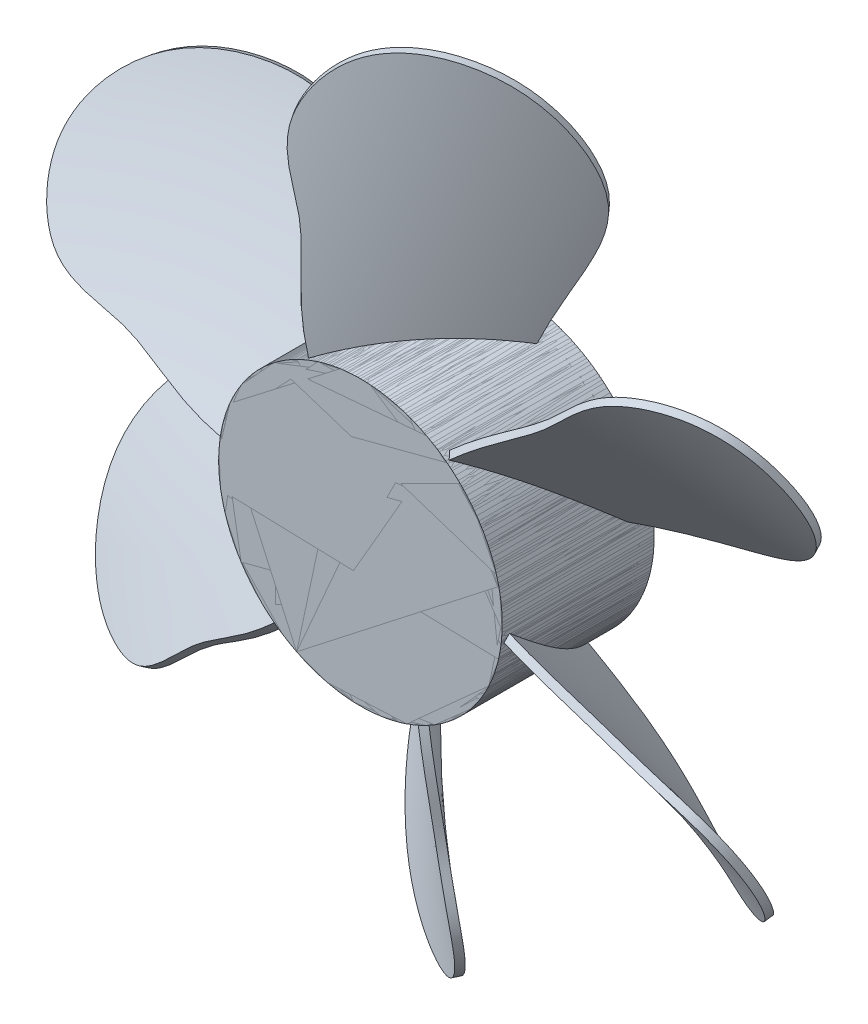
SolidWorks part; units mm, degrees
ref_plane "前视基准面" through (0, 0, 0) normal (0, 0, 1) x (1, 0, 0)
ref_plane "上视基准面" through (0, 0, 0) normal (0, 1, 0) x (1, 0, 0)
ref_plane "右视基准面" through (0, 0, 0) normal (1, 0, 0) x (0, 0, -1)
sketch "草图1" plane through (0, 0, 0) normal (0, 0, 1) x (1, 0, 0)
  circle A0 centre (0, 0) radius 9.3333
  dimension "D1" = 18.6667
extrude "凸台-拉伸1" add sketch "草图1" along normal blind 10
sketch "草图2" plane through (0, 0, 0) normal (0, 1, 0) x (1, 0, 0)
  line L0 (0, 1.5142) -> (0, -11.6911) construction
  line L1 (4.7105, 3.0704) -> (-4.7105, -13.2473)
  point P5 (0, -5.0884)
  dimension "D1" = 30
ref_plane "基准面1" through (0, 26, 0) normal (0, 1, 0) x (1, 0, 0)
sketch "草图3" plane through (0, 26, 0) normal (0, 1, 0) x (1, 0, 0)
  line L0 (8.1051, -0.4089) -> (-8.1051, -9.7679)
  line L1 (0, 1.5142) -> (0, -11.6911) construction
  point P2 (0, -5.0884)
  dimension "D1" = 60
surface "曲面-放样1"
sketch "草图5" plane through (0, 0, 0) normal (0, 0, 1) x (1, 0, 0)
  circle A0 centre (0, 0) radius 9.3333 construction
  spline S0 degree 3 poles (-4.5786, 9.4781) (0.3126, -5.7872) (2.5361, 10.4591) (7.7001, 16.7271) (4.2326, 25.1527) (-2.9046, 26.0682) (-6.3302, 20.9309) (-4.3738, 15.878) (-4.5786, 9.4781) (0.3126, -5.7872) (2.5361, 10.4591) knots -0.372375 -0.289372 -0.197727 0 0.159159 0.330157 0.443222 0.547935 0.627625 0.710628 0.802273 1 1.159159 1.330157 1.443222 only from (0, 0) to (0, 0)
surface "曲面-剪裁1"
thicken "加厚1" surfaces to thicken 108 thickness 0.25 thickness side both sides parameters "D1"=0.25
pattern_circular "阵列(圆周)3" count 6 over 360 about axis through (0, 0, 10) along (0, 0, -1) of bodies 109
fillet "圆角1" radius 1 1 edges at (-4.6667, 8.0829, 0)
